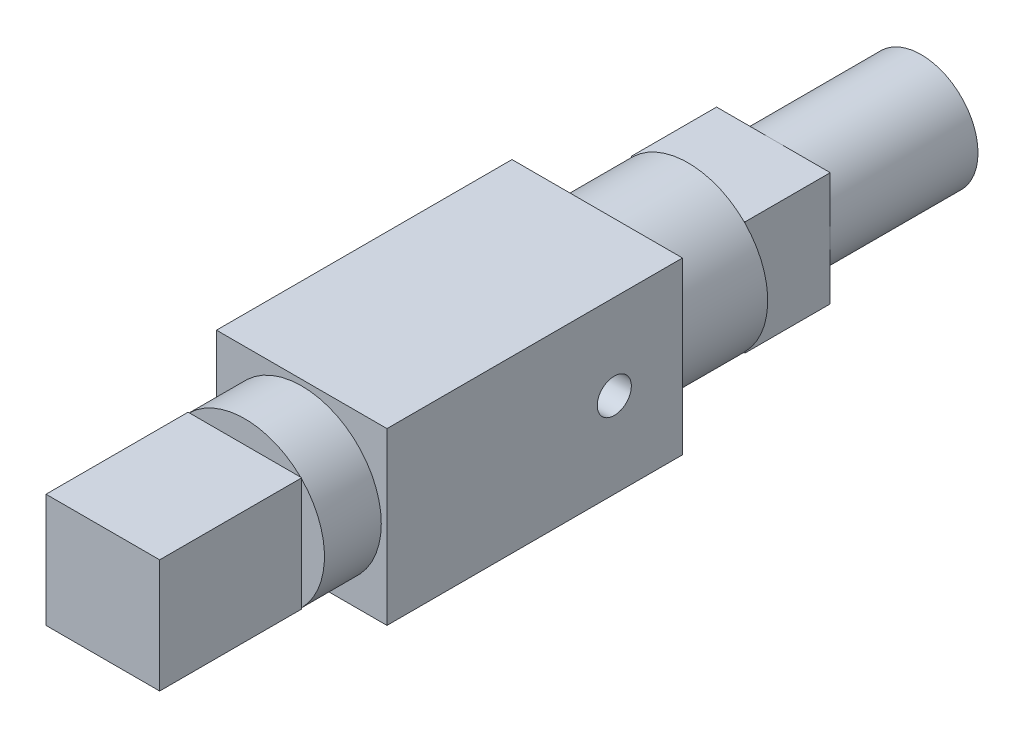
SolidWorks part; units mm, degrees
ref_plane "Piano frontale" through (0, 0, 0) normal (0, 0, 1) x (1, 0, 0)
ref_plane "Piano superiore" through (0, 0, 0) normal (0, 1, 0) x (1, 0, 0)
ref_plane "Piano destro" through (0, 0, 0) normal (1, 0, 0) x (0, 0, -1)
sketch "Schizzo1" plane through (0, 0, 0) normal (0, 0, 1) x (1, 0, 0)
  circle A0 centre (0, 0) radius 5
  dimension "D1" = 10
extrude "Estrusione-Estrusione1" add sketch "Schizzo1" along normal blind 13
sketch "Schizzo2" plane through (0, 0, 13) normal (0, 0, 1) x (1, 0, 0)
  line L1 (5, -5) -> (-5, -5)
  line L2 (5, -5) -> (5, 5)
  line L3 (5, 5) -> (-5, 5)
  line L4 (-5, -5) -> (-5, 5)
  line L5 (5, -5) -> (-5, 5) construction
  line L6 (5, 5) -> (-5, -5) construction
  point P0 (0, 0)
  dimension "D1" = 10
  dimension "D2" = 10
extrude "Estrusione-Estrusione2" add sketch "Schizzo2" along normal blind 7.5
sketch "Schizzo3" plane through (0, 0, 20.5) normal (0, 0, 1) x (1, 0, 0)
  circle A0 centre (0, 0) radius 7
  dimension "D1" = 14
extrude "Estrusione-Estrusione3" add sketch "Schizzo3" along normal blind 8
sketch "Schizzo4" plane through (0, 0, 28.5) normal (0, 0, 1) x (1, 0, 0)
  line L1 (7.5, -7.5) -> (-7.5, -7.5)
  line L2 (7.5, -7.5) -> (7.5, 7.5)
  line L3 (7.5, 7.5) -> (-7.5, 7.5)
  line L4 (-7.5, -7.5) -> (-7.5, 7.5)
  line L5 (7.5, -7.5) -> (-7.5, 7.5) construction
  line L6 (7.5, 7.5) -> (-7.5, -7.5) construction
  point P0 (0, 0)
  dimension "D1" = 15
  dimension "D2" = 15
extrude "Estrusione-Estrusione4" add sketch "Schizzo4" along normal blind 26
sketch "Schizzo5" plane through (0, 0, 54.5) normal (0, 0, 1) x (1, 0, 0)
  circle A0 centre (0, 0) radius 7
  dimension "D1" = 14
extrude "Estrusione-Estrusione5" add sketch "Schizzo5" along normal blind 5
sketch "Schizzo6" plane through (0, 0, 59.5) normal (0, 0, 1) x (1, 0, 0)
  line L1 (5, -5) -> (-5, -5)
  line L2 (5, -5) -> (5, 5)
  line L3 (5, 5) -> (-5, 5)
  line L4 (-5, -5) -> (-5, 5)
  line L5 (5, -5) -> (-5, 5) construction
  line L6 (5, 5) -> (-5, -5) construction
  point P0 (0, 0)
  dimension "D1" = 10
  dimension "D2" = 10
extrude "Estrusione-Estrusione6" add sketch "Schizzo6" along normal blind 12.5
dome "Cupola1" faces to dome 1 distance 1.3 reverse direction no elliptical dome no face at (5, 0, 0) parameters "D1"=1.3
sketch "Schizzo7" plane through (-7.5, 0, 0) normal (-1, 0, 0) x (0, 0, 1)
  line L1 (28.5, 7.5) -> (28.5, -7.5) construction
  circle A0 centre (34.5, 0) radius 1.5
  dimension "D1" = 3
  dimension "D2" = 6
extrude "Taglio-Estrusione1" cut sketch "Schizzo7" against normal through all
